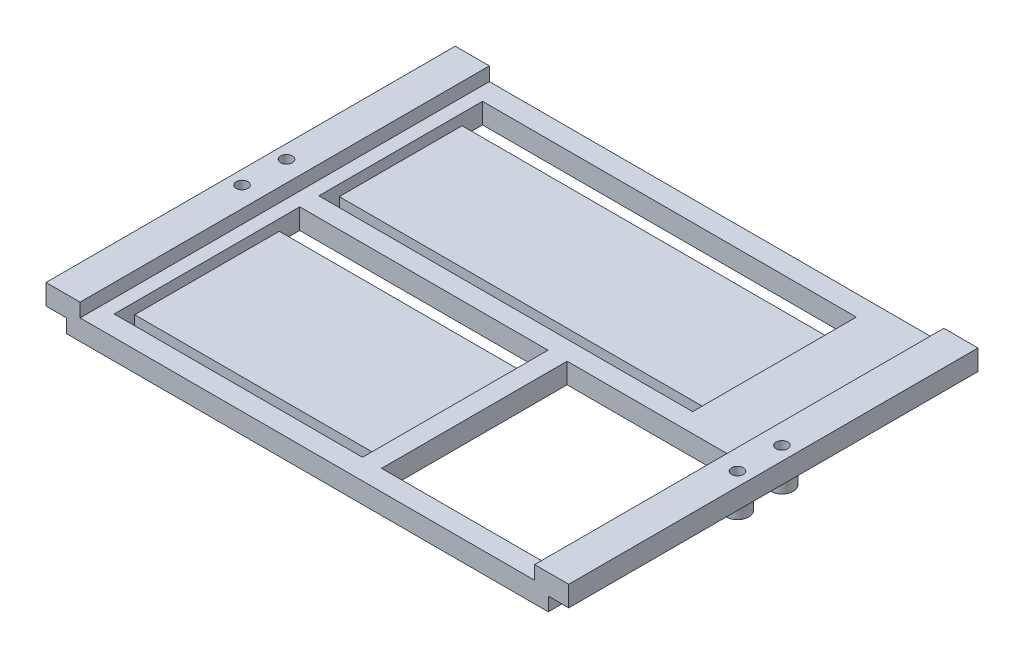
SolidWorks part; units mm, degrees
ref_plane "Front Plane" through (0, 0, 0) normal (0, 0, 1) x (1, 0, 0)
ref_plane "Top Plane" through (0, 0, 0) normal (0, 1, 0) x (1, 0, 0)
ref_plane "Right Plane" through (0, 0, 0) normal (1, 0, 0) x (0, 0, -1)
sketch "Sketch2" plane through (0, 0, 0) normal (0, 0, 1) x (1, 0, 0)
  line L0 (179.1, 12.5) -> (191.6, 12.5)
  line L1 (7.5, 0) -> (184.1, 0)
  line L2 (0, 5) -> (0, 12.5)
  line L3 (0, 12.5) -> (12.5, 12.5)
  line L4 (191.6, 5) -> (191.6, 12.5)
  line L7 (0, 5) -> (7.5, 5)
  line L8 (7.5, 0) -> (7.5, 5)
  line L11 (191.6, 5) -> (184.1, 5)
  line L12 (184.1, 0) -> (184.1, 5)
  line L14 (12.5, 12.5) -> (12.5, 7.5)
  line L15 (12.5, 7.5) -> (179.1, 7.5)
  line L16 (179.1, 12.5) -> (179.1, 7.5)
  dimension "D1" = 191.6
  dimension "D2" = 5
  dimension "D3" = 5
  dimension "D4" = 5
  dimension "D5" = 12.5
  dimension "D6" = 7.5
  dimension "D7" = 7.5
  dimension "D8" = 12.5
  dimension "D9" = 12.5
extrude "PlateFrame" add sketch "Sketch2" along normal blind 150
sketch "Sketch3" plane through (0, 12.5, 0) normal (0, 1, 0) x (1, 0, 0)
  line L0 (12.5, 0) -> (0, 0) construction
  line L2 (0, -150) -> (0, 0) construction
  line L3 (191.6, -150) -> (191.6, 0) construction
  line L4 (191.6, 0) -> (179.1, 0) construction
  circle A0 centre (5, -66.85) radius 2.15
  circle A1 centre (5, -83.15) radius 2.15
  circle A2 centre (186.6, -66.85) radius 2.15
  circle A3 centre (186.6, -83.15) radius 2.15
  dimension "D1" = 4.3
  dimension "D2" = 4.3
  dimension "D3" = 4.3
  dimension "D4" = 4.3
  dimension "D5" = 66.85
  dimension "D6" = 16.3
  dimension "D7" = 5
  dimension "D8" = 5
  dimension "D9" = 5
  dimension "D10" = 181.6
  dimension "D11" = 66.85
  dimension "D12" = 16.3
extrude "HoleSupport" cut sketch "Sketch3" against normal blind 7.5
sketch "Sketch4" plane through (0, 12.5, 0) normal (0, 1, 0) x (1, 0, 0)
  circle A0 centre (5, -66.85) radius 2.15
  circle A1 centre (5, -83.15) radius 2.15
  circle A2 centre (186.6, -83.15) radius 2.15
  circle A3 centre (186.6, -66.85) radius 2.15
  circle A4 centre (186.6, -66.85) radius 4.15
  circle A5 centre (186.6, -83.15) radius 4.15
  circle A6 centre (5, -66.85) radius 4.15
  circle A7 centre (5, -83.15) radius 4.15
  dimension "D1" = 2
extrude "CylindricalSupports" add sketch "Sketch4" against normal blind 12.5
sketch "Sketch8" plane through (0, 7.5, 0) normal (0, 1, 0) x (1, 0, 0)
  line L0 (12.5, -150) -> (12.5, 0) construction
  line L2 (154.5, -7.5) -> (17.5, -7.5)
  line L3 (154.5, -7.5) -> (154.5, -67.5)
  line L4 (154.5, -67.5) -> (17.5, -67.5)
  line L5 (17.5, -7.5) -> (17.5, -67.5)
  line L6 (108.5, -142.5) -> (17.5, -142.5)
  line L7 (108.5, -142.5) -> (108.5, -74.5)
  line L8 (108.5, -74.5) -> (17.5, -74.5)
  line L9 (17.5, -142.5) -> (17.5, -74.5)
  line L10 (179.1, 0) -> (12.5, 0) construction
  line L11 (179.1, -150) -> (12.5, -150) construction
  dimension "D1" = 5
  dimension "D2" = 7.5
  dimension "D3" = 7.5
  dimension "D4" = 5
  dimension "D5" = 60
  dimension "D6" = 68
  dimension "D7" = 137
  dimension "D8" = 91
extrude "ItemLayout" cut sketch "Sketch8" against normal blind 4
sketch "Sketch9" plane through (0, 7.5, 0) normal (0, 1, 0) x (1, 0, 0)
  line L0 (179.1, -150) -> (179.1, 0) construction
  line L1 (115.5, -74.5) -> (174.1, -74.5)
  line L2 (115.5, -74.5) -> (115.5, -142.5)
  line L3 (115.5, -142.5) -> (174.1, -142.5)
  line L4 (174.1, -74.5) -> (174.1, -142.5)
  line L5 (179.1, -150) -> (12.5, -150) construction
  line L7 (108.5, -142.5) -> (108.5, -74.5) construction
  dimension "D1" = 5
  dimension "D2" = 7.5
  dimension "D3" = 68
  dimension "D4" = 7
extrude "HoleCutout" cut sketch "Sketch9" against normal blind 7.5
sketch "Sketch10" plane through (0, 3.5, 0) normal (0, 1, 0) x (1, 0, 0)
  line L0 (108.5, -142.5) -> (108.5, -74.5) construction
  line L1 (17.5, -74.5) -> (108.5, -74.5)
  line L2 (17.5, -74.5) -> (17.5, -82)
  line L3 (17.5, -82) -> (108.5, -82)
  line L4 (108.5, -74.5) -> (108.5, -82)
  line L5 (108.5, -142.5) -> (108.5, -74.5) construction
  line L6 (17.5, -142.5) -> (108.5, -142.5)
  line L7 (17.5, -142.5) -> (17.5, -135)
  line L8 (17.5, -135) -> (108.5, -135)
  line L9 (108.5, -142.5) -> (108.5, -135)
  line L10 (154.5, -67.5) -> (154.5, -7.5) construction
  line L11 (17.5, -7.5) -> (154.5, -7.5)
  line L12 (17.5, -7.5) -> (17.5, -15)
  line L13 (17.5, -15) -> (154.5, -15)
  line L14 (154.5, -7.5) -> (154.5, -15)
  line L16 (17.5, -67.5) -> (154.5, -67.5)
  line L17 (17.5, -67.5) -> (17.5, -60)
  line L18 (17.5, -60) -> (154.5, -60)
  line L19 (154.5, -67.5) -> (154.5, -60)
  dimension "D1" = 7.5
  dimension "D2" = 7.5
  dimension "D3" = 7.5
  dimension "D4" = 7.5
extrude "VelcroCut" cut sketch "Sketch10" against normal blind 3.5
